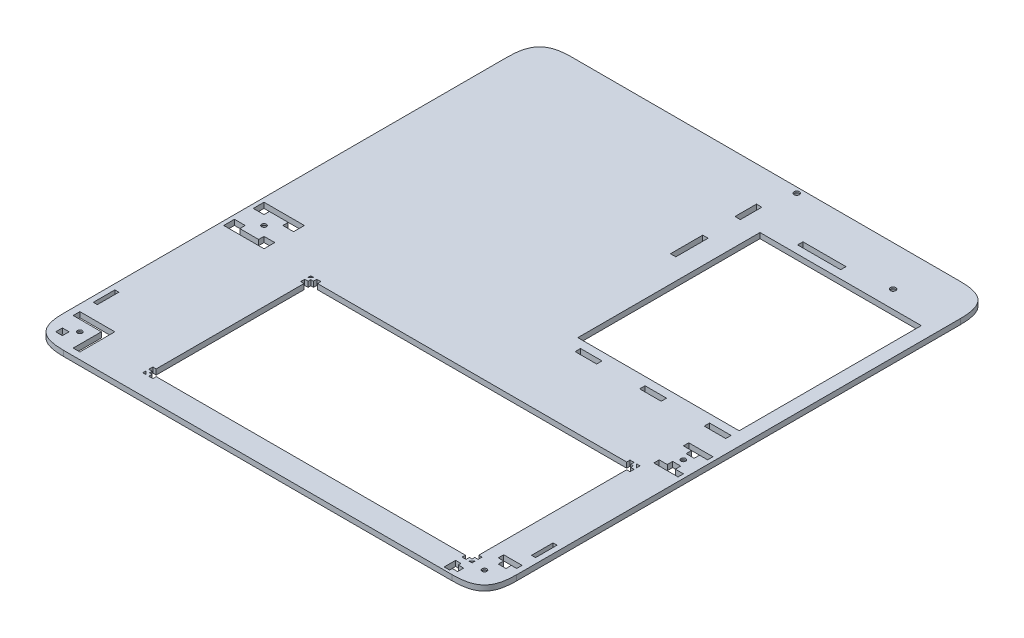
SolidWorks part; units mm, degrees
ref_plane "Front Plane" through (0, 0, 0) normal (0, 0, 1) x (1, 0, 0)
ref_plane "Top Plane" through (0, 0, 0) normal (0, 1, 0) x (1, 0, 0)
ref_plane "Right Plane" through (0, 0, 0) normal (1, 0, 0) x (0, 0, -1)
sketch "Sketch1" plane through (0, 0, 0) normal (0, 1, 0) x (1, 0, 0)
  line L1 (0, 0) -> (337, 0)
  line L2 (0, 0) -> (0, 377.97)
  line L3 (0, 377.97) -> (337, 377.97)
  line L4 (337, 0) -> (337, 377.97)
  line L5 (70.28, 137.5) -> (310.28, 137.5)
  line L6 (70.28, 137.5) -> (70.28, 17.5)
  line L7 (70.28, 17.5) -> (310.28, 17.5)
  line L8 (310.28, 137.5) -> (310.28, 17.5)
  dimension "D1" = 337
  dimension "D2" = 377.97
  dimension "D3" = 240
  dimension "D4" = 120
  dimension "D5" = 17.5
  dimension "D6" = 26.72
extrude "Boss-Extrude1" add sketch "Sketch1" against normal blind 4
fillet "Fillet1" radius 24 4 edges at (0, -2, 0) (337, -2, 0) (0, -2, -377.97) (337, -2, -377.97) conic rho 0.55
sketch "Sketch3" plane through (0, 0, 0) normal (0, 1, 0) x (1, 0, 0)
  line L0 (337, 24) -> (337, 353.97) construction
  line L1 (24, 0) -> (313, 0) construction
  line L2 (0, 353.97) -> (0, 24) construction
  line L3 (309, 4) -> (309, 2)
  line L4 (305, 10.5) -> (309, 10.5)
  line L5 (305, 10.5) -> (305, 2)
  line L6 (305, 2) -> (309, 2)
  line L7 (309, 10.5) -> (309, 8.5)
  line L8 (309, 8.5) -> (313, 8.5)
  line L10 (309, 4) -> (313, 4)
  line L11 (313, 8.5) -> (313, 4)
  line L12 (329, 28) -> (333, 28)
  line L13 (319.28, 32) -> (333, 32)
  line L14 (319.28, 32) -> (319.28, 28)
  line L15 (319.28, 28) -> (323.28, 28)
  line L16 (333, 32) -> (333, 28)
  line L18 (323.28, 28) -> (323.28, 24)
  line L19 (323.28, 24) -> (329, 24)
  line L20 (329, 28) -> (329, 24)
  line L21 (328, 151) -> (334, 151)
  line L30 (26, 5) -> (31, 5)
  line L36 (26, 5) -> (26, 26)
  line L37 (9, 14) -> (14, 14)
  line L38 (9, 14) -> (9, 9)
  line L39 (9, 9) -> (14, 9)
  line L40 (14, 14) -> (14, 9)
  line L41 (26, 31) -> (31, 31)
  line L42 (31, 5) -> (31, 31)
  line L43 (26, 31) -> (5, 31)
  line L45 (26, 26) -> (5, 26)
  line L46 (5, 31) -> (5, 26)
  line L47 (3, 140) -> (33, 140)
  line L48 (3, 140) -> (3, 144)
  line L49 (11, 144) -> (25, 144)
  line L50 (33, 140) -> (33, 144)
  line L52 (3, 144) -> (3, 148)
  line L53 (3, 148) -> (11, 148)
  line L54 (11, 144) -> (11, 148)
  line L56 (33, 144) -> (33, 148)
  line L57 (33, 148) -> (25, 148)
  line L58 (25, 144) -> (25, 148)
  line L59 (3, 170) -> (33, 170)
  line L60 (3, 170) -> (3, 166)
  line L61 (11, 166) -> (25, 166)
  line L62 (33, 170) -> (33, 166)
  line L64 (3, 166) -> (3, 162)
  line L65 (3, 162) -> (11, 162)
  line L66 (11, 166) -> (11, 162)
  line L68 (33, 166) -> (33, 162)
  line L69 (33, 162) -> (25, 162)
  line L70 (25, 166) -> (25, 162)
  line L71 (316, 147) -> (334, 147)
  line L72 (316, 147) -> (316, 151)
  line L73 (316, 151) -> (322, 151)
  line L74 (334, 147) -> (334, 151)
  line L76 (322, 151) -> (322, 155)
  line L77 (322, 155) -> (328, 155)
  line L78 (328, 151) -> (328, 155)
  line L79 (328, 169) -> (334, 169)
  line L80 (316, 173) -> (334, 173)
  line L81 (316, 173) -> (316, 169)
  line L82 (316, 169) -> (322, 169)
  line L83 (334, 173) -> (334, 169)
  line L85 (322, 169) -> (322, 165)
  line L86 (322, 165) -> (328, 165)
  line L87 (328, 169) -> (328, 165)
  line L88 (313, 377.97) -> (24, 377.97) construction
  line L89 (333, 42) -> (330, 42)
  line L90 (333, 42) -> (333, 58)
  line L91 (333, 58) -> (330, 58)
  line L92 (330, 42) -> (330, 58)
  line L93 (4, 42) -> (7, 42)
  line L94 (4, 42) -> (4, 58)
  line L95 (4, 58) -> (7, 58)
  line L96 (7, 42) -> (7, 58)
  line L97 (187.4, 351.97) -> (191.4, 351.97)
  line L98 (187.4, 351.97) -> (187.4, 335.97)
  line L99 (187.4, 335.97) -> (191.4, 335.97)
  line L100 (191.4, 351.97) -> (191.4, 335.97)
  line L102 (187.4, 311.97) -> (191.4, 311.97)
  line L103 (187.4, 311.97) -> (187.4, 287.97)
  line L104 (187.4, 287.97) -> (191.4, 287.97)
  line L105 (191.4, 311.97) -> (191.4, 287.97)
  line L106 (207, 334.97) -> (327, 334.97)
  line L107 (207, 334.97) -> (207, 199.47)
  line L108 (207, 199.47) -> (327, 199.47)
  line L109 (327, 334.97) -> (327, 199.47)
  line L110 (327, 193.47) -> (311, 193.47)
  line L111 (327, 193.47) -> (327, 189.47)
  line L112 (327, 189.47) -> (311, 189.47)
  line L113 (311, 193.47) -> (311, 189.47)
  line L114 (279, 193.47) -> (263, 193.47)
  line L115 (279, 193.47) -> (279, 189.47)
  line L116 (279, 189.47) -> (263, 189.47)
  line L117 (263, 193.47) -> (263, 189.47)
  line L118 (231, 193.47) -> (215, 193.47)
  line L119 (231, 193.47) -> (231, 189.47)
  line L120 (231, 189.47) -> (215, 189.47)
  line L121 (215, 193.47) -> (215, 189.47)
  line L122 (229, 344.97) -> (261, 344.97)
  line L123 (229, 344.97) -> (229, 340.97)
  line L124 (229, 340.97) -> (261, 340.97)
  line L125 (261, 344.97) -> (261, 340.97)
  circle A0 centre (322, 15) radius 1.75
  circle A1 centre (18, 18) radius 1.75
  circle A2 centre (18, 155) radius 1.75
  circle A3 centre (325, 160) radius 1.75
  circle A4 centre (195.4, 373.97) radius 2
  circle A5 centre (293, 347.97) radius 2
  point P37 (5, 28.5)
  dimension "D3" = 3.5
  dimension "D6" = 3.5
  dimension "D45" = 3.5
  dimension "D62" = 3.5
  dimension "D79" = 4
  dimension "D80" = 4
  dimension "D81" = 4
  dimension "D100" = 4
  dimension "D101" = 44
  dimension "D1" = 15
  dimension "D2" = 15
  dimension "D4" = 18
  dimension "D5" = 18
  dimension "D7" = 24
  dimension "D8" = 4
  dimension "D9" = 2
  dimension "D10" = 2
  dimension "D11" = 4.5
  dimension "D12" = 2
  dimension "D13" = 4
  dimension "D14" = 4
  dimension "D15" = 13.72
  dimension "D16" = 4
  dimension "D17" = 4
  dimension "D18" = 4
  dimension "D19" = 4
  dimension "D20" = 24
  dimension "D21" = 5
  dimension "D22" = 5
  dimension "D23" = 9
  dimension "D24" = 9
  dimension "D25" = 26
  dimension "D26" = 5
  dimension "D27" = 5
  dimension "D28" = 5
  dimension "D29" = 21
  dimension "D30" = 5
  dimension "D31" = 30
  dimension "D32" = 4
  dimension "D33" = 4
  dimension "D34" = 8
  dimension "D35" = 8
  dimension "D36" = 4
  dimension "D37" = 30
  dimension "D38" = 4
  dimension "D39" = 4
  dimension "D40" = 4
  dimension "D41" = 30
  dimension "D42" = 140
  dimension "D43" = 3
  dimension "D44" = 3
  dimension "D46" = 11
  dimension "D47" = 4
  dimension "D48" = 4
  dimension "D49" = 4
  dimension "D50" = 18
  dimension "D51" = 3
  dimension "D52" = 6
  dimension "D53" = 6
  dimension "D54" = 4
  dimension "D55" = 4
  dimension "D56" = 4
  dimension "D57" = 18
  dimension "D58" = 6
  dimension "D59" = 6
  dimension "D60" = 10
  dimension "D61" = 147
  dimension "D63" = 5
  dimension "D64" = 9
  dimension "D65" = 3
  dimension "D66" = 16
  dimension "D67" = 10
  dimension "D68" = 4
  dimension "D69" = 4
  dimension "D70" = 16
  dimension "D71" = 3
  dimension "D72" = 0
  dimension "D73" = 145.6
  dimension "D74" = 26
  dimension "D75" = 4
  dimension "D76" = 16
  dimension "D77" = 24
  dimension "D78" = 24
  dimension "D82" = 43
  dimension "D83" = 10
  dimension "D84" = 135.5
  dimension "D85" = 120
  dimension "D86" = 4
  dimension "D87" = 6
  dimension "D88" = 16
  dimension "D89" = 10
  dimension "D90" = 16
  dimension "D91" = 32
  dimension "D92" = 4
  dimension "D93" = 6
  dimension "D94" = 16
  dimension "D95" = 32
  dimension "D96" = 32
  dimension "D97" = 4
  dimension "D98" = 6
  dimension "D99" = 76
  dimension "D102" = 13
extrude "Cut-Extrude1" cut sketch "Sketch3" against normal up to next
ref_plane "Plane3" through (190.28, 0, 0) normal (-1, 0, 0) x (0, 0, 1)
ref_plane "Plane6" through (0, 0, -77.5) normal (0, 0, 1) x (1, 0, 0)
sketch "Sketch5" plane through (0, 0, 0) normal (0, 1, 0) x (1, 0, 0)
  line L0 (310.28, 17.5) -> (310.28, 137.5) construction
  line L3 (310.28, 15) -> (312.78, 15)
  line L4 (312.78, 17.5) -> (312.78, 15)
  line L5 (310.28, 22.5) -> (312.78, 22.5)
  line L6 (310.28, 22.5) -> (310.28, 19.5)
  line L7 (310.28, 19.5) -> (312.78, 19.5)
  line L8 (312.78, 22.5) -> (312.78, 19.5)
  line L9 (70.28, 17.5) -> (310.28, 17.5) construction
  line L10 (305.28, 17.5) -> (308.28, 17.5)
  line L11 (305.28, 17.5) -> (305.28, 15)
  line L12 (305.28, 15) -> (308.28, 15)
  line L13 (308.28, 17.5) -> (308.28, 15)
  line L14 (310.28, 15) -> (312.78, 17.5)
  dimension "D1" = 2.5
  dimension "D2" = 2.5
  dimension "D4" = 3
  dimension "D6" = 3
extrude "Cut-Extrude2" cut sketch "Sketch5" against normal up to next
mirror "Mirror1" about plane through (0, 0, -77.5) normal (0, 0, 1) of "Cut-Extrude2" second plane through (190.28, 0, 0) second plane normal (-1, 0, 0)
sketch "Sketch6" plane through (0, -4, 0) normal (0, -1, 0) x (1, 0, 0)
  circle A0 centre (18, -155) radius 3.5
  circle A1 centre (18, -18) radius 3.5
  circle A2 centre (322, -15) radius 3.5
  circle A3 centre (325, -160) radius 3.5
  circle A4 centre (195.4, -373.97) radius 3.5
  circle A5 centre (293, -347.97) radius 3.5
  dimension "D1" = 7
  dimension "D2" = 7
  dimension "D3" = 7
  dimension "D4" = 7
  dimension "D5" = 7
  dimension "D6" = 7
extrude "Cut-Extrude3" cut sketch "Sketch6" against normal blind 2.8
